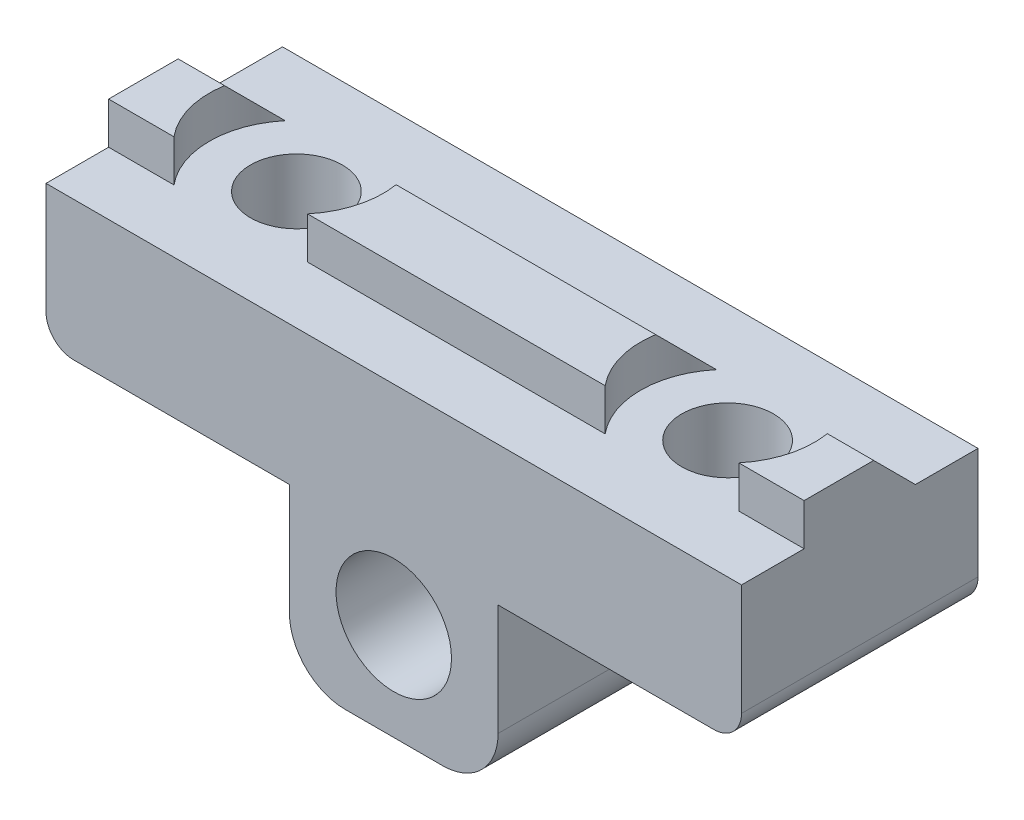
SolidWorks part; units mm, degrees
ref_plane "Přední rovina" through (0, 0, 0) normal (0, 0, 1) x (1, 0, 0)
ref_plane "Horní rovina" through (0, 0, 0) normal (0, 1, 0) x (1, 0, 0)
ref_plane "Pravá rovina" through (0, 0, 0) normal (1, 0, 0) x (0, 0, -1)
sketch "Skica1" plane through (0, 0, 0) normal (0, 0, 1) x (1, 0, 0)
  line L0 (0, 0) -> (50, 0)
  line L1 (50, 0) -> (50, -8)
  line L2 (17.5, -22) -> (17.5, -10)
  line L3 (17.5, -10) -> (2, -10)
  line L4 (32.5, -22) -> (17.5, -22)
  line L5 (32.5, -22) -> (32.5, -10)
  line L6 (32.5, -10) -> (48, -10)
  line L7 (0, -8) -> (0, 0)
  arc A0 (0, -8) -> (2, -10) centre (2, -8) ccw
  arc A1 (50, -8) -> (48, -10) centre (48, -8) cw
  point P9 (0, -10)
  point P14 (50, -10)
  dimension "D3" = 10
  dimension "D6" = 2
  dimension "D1" = 50
  dimension "D2" = 15
  dimension "D4" = 22
  dimension "D5" = 10
extrude "Přidat vysunutím1" add sketch "Skica1" along normal blind 17
sketch "Skica2" plane through (0, 0, 17) normal (0, 0, 1) x (1, 0, 0)
  line L1 (25, -25) -> (25, 0)
  line L2 (50, 0) -> (0, 0) construction
  point P8 (25, -15)
  dimension "D1" = 15
hole_wizard "Válcové zahloubení pro M6 šrouby s hlavou s vnitřním vybráním1" positions "Skica3" profile "Skica4" counterbore size "M6" standard "DIN" end condition through all
sketch "Skica3" plane through (0, 0, 17) normal (0, 0, 1) x (1, 0, 0)
  point P0 (25, -15)
sketch "Skica4" plane through (25, -15, 17) normal (1, 0, 0) x (0, -1, 0)
  line L0 (0, 0) -> (0, 17)
  line L1 (0, 17) -> (3.3, 17)
  line L3 (3.3, 17) -> (3.3, 10)
  line L4 (3.3, 10) -> (4.15, 10)
  line L5 (4.15, 10) -> (4.15, 0)
  line L7 (4.15, 0) -> (0, 0)
  line L11 (0, -6.35) -> (0, 107.95) construction
  dimension "Průměr díry skrz" = 6.6
  dimension "Hloubka díry skrz" = 17
  dimension "Průměr válcového zahloubení" = 8.3
  dimension "Hloubka válcového zahloubení" = 10
sketch "Skica5" plane through (0, -10, 0) normal (0, -1, 0) x (1, 0, 0)
  line L0 (9.5, 0) -> (9.5, 17)
  line L3 (2, 0) -> (17.5, 0) construction
  line L4 (25, 0) -> (25, 26.4222)
  line L5 (2, 17) -> (17.5, 17) construction
  point P7 (9.5, 8.5)
  point P8 (40.5, 8.5)
  dimension "D1" = 8
  dimension "D2" = 7.5
hole_wizard "Válcové zahloubení pro M6 šrouby s hlavou s vnitřním vybráním2" positions "Skica8" profile "Skica9" counterbore size "M6" standard "DIN" end condition through all
sketch "Skica8" plane through (0, -10, 0) normal (0, -1, 0) x (-1, 0, 0)
  point P0 (-9.5, -8.5)
  point P3 (-40.5, -8.5)
sketch "Skica9" plane through (9.5, -10, 8.5) normal (1, 0, 0) x (0, 0, -1)
  line L0 (0, 0) -> (0, 10)
  line L1 (0, 10) -> (3.3, 10)
  line L3 (3.3, 10) -> (3.3, 2)
  line L4 (3.3, 2) -> (6, 2)
  line L5 (6, 2) -> (6, 0)
  line L7 (6, 0) -> (0, 0)
  line L11 (0, -6.35) -> (0, 107.95) construction
  dimension "Průměr díry skrz" = 6.6
  dimension "Hloubka díry skrz" = 10
  dimension "Průměr válcového zahloubení" = 12
  dimension "Hloubka válcového zahloubení" = 2
fillet "Zaoblit1" radius 4 2 edges at (17.5, -22, 8.5) (32.5, -22, 8.5)
sketch "Skica10" plane through (0, 0, 0) normal (0, 1, 0) x (1, 0, 0)
  line L0 (50, -8.5) -> (0, -8.5)
  line L1 (50, -17) -> (50, 0) construction
  line L2 (0, -17) -> (0, 0) construction
  line L4 (50, -4.5) -> (0, -4.5)
  line L5 (50, -4.5) -> (50, -12.5)
  line L6 (50, -12.5) -> (0, -12.5)
  line L7 (0, -4.5) -> (0, -12.5)
  line L8 (50, -4.5) -> (0, -12.5) construction
  line L9 (50, -12.5) -> (0, -4.5) construction
  circle A0 centre (9.5, -8.5) radius 6.25
  circle A1 centre (40.5, -8.5) radius 6.25
  point P6 (25, -8.5)
  line M5 (0, 0) -> (0, -17)
  line M7 (50, -17) -> (50, 0)
  dimension "D2" = 12.5
  dimension "D1" = 8
extrude "Přidat vysunutím4" add sketch "Skica10" along normal blind 3 contours A1 L4 A0 L0 | A1 L0 A0 L6 | A0 L0 L6 M5 | A0 L4 L0 M5 | A1 L0 L4 M7 | A1 L6 L0 M7
chamfer "Zkosení1" distance 3 angle 45 9 edges at (35.6977, 1.5, 4.5) (14.3023, 1.5, 4.5) (25, 3, 4.5) (4.6977, 1.5, 4.5) (0, 1.5, 4.5) (2.3488, 3, 4.5) (45.3023, 1.5, 4.5) (50, 1.5, 4.5) (47.6512, 3, 4.5)
